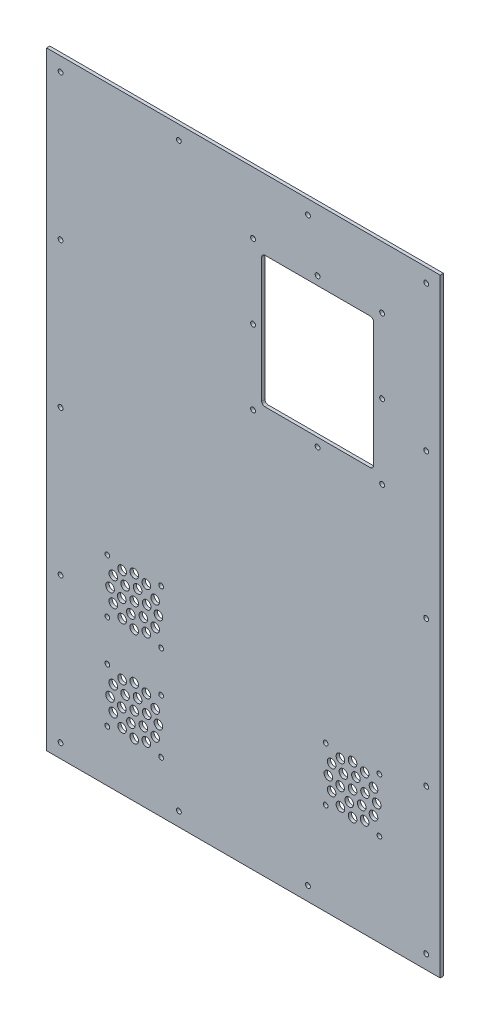
SolidWorks part; units mm, degrees
ref_plane "Спереди" through (0, 0, 0) normal (0, 0, 1) x (1, 0, 0)
ref_plane "Сверху" through (0, 0, 0) normal (0, 1, 0) x (1, 0, 0)
ref_plane "Справа" through (0, 0, 0) normal (1, 0, 0) x (0, 0, -1)
sketch "Эскиз1" plane through (0, 0, 0) normal (0, 0, 1) x (1, 0, 0)
  line L0 (0, 0) -> (366, 0)
  line L1 (0, 0) -> (0, 566)
  line L2 (366, 0) -> (366, 566)
  line L3 (0, 566) -> (366, 566)
  dimension "D1" = 566
  dimension "D2" = 366
extrude "Бобышка-Вытянуть1" add sketch "Эскиз1" along normal blind 3
sketch "Эскиз2" plane through (0, 0, 3) normal (0, 0, 1) x (1, 0, 0)
  line L0 (3, 563) -> (363, 563) construction
  line L1 (3, 563) -> (3, 3) construction
  line L2 (363, 563) -> (363, 3) construction
  line L3 (3, 3) -> (363, 3) construction
  line L4 (0, 566) -> (0, 0) construction
  line L5 (0, 0) -> (366, 0) construction
  dimension "D1" = 560
  dimension "D2" = 360
  dimension "D3" = 3
  dimension "D4" = 3
sketch "Эскиз5" plane through (0, 0, 0) normal (0, 0, -1) x (-1, 0, 0)
  line L0 (-353, 553) -> (-13, 553) construction
  line L1 (-353, 553) -> (-353, 13) construction
  line L2 (-13, 553) -> (-13, 13) construction
  line L3 (-353, 13) -> (-13, 13) construction
  line L4 (-366, 566) -> (0, 566) construction
  line L5 (-366, 0) -> (-366, 566) construction
  line L6 (0, 566) -> (0, 0) construction
  line L7 (0, 0) -> (-366, 0) construction
  line L8 (-366, 23) -> (-343, 23) construction
  line L9 (-366, 23) -> (-366, 0) construction
  line L10 (-343, 23) -> (-343, 0) construction
  line L11 (-366, 0) -> (-343, 0) construction
  line L12 (0, 0) -> (0, 23) construction
  line L13 (0, 0) -> (-23, 0) construction
  line L14 (0, 23) -> (-23, 23) construction
  line L15 (-23, 0) -> (-23, 23) construction
  line L16 (-366, 566) -> (-343, 566) construction
  line L17 (-366, 566) -> (-366, 543) construction
  line L18 (-343, 566) -> (-343, 543) construction
  line L19 (-366, 543) -> (-343, 543) construction
  line L20 (0, 566) -> (0, 543) construction
  line L21 (0, 566) -> (-23, 566) construction
  line L22 (0, 543) -> (-23, 543) construction
  line L23 (-23, 566) -> (-23, 543) construction
  line L24 (-13, 283) -> (-353, 283) construction
  line L25 (-183, 553) -> (-183, 13) construction
  circle A0 centre (-353, 553) radius 2.25
  circle A1 centre (-13, 553) radius 2.25
  circle A3 centre (-243, 553) radius 2.25
  circle A4 centre (-123, 553) radius 2.25
  circle A5 centre (-353, 418) radius 2.25
  circle A6 centre (-353, 283) radius 2.25
  circle A7 centre (-353, 148) radius 2.25
  circle A8 centre (-353, 13) radius 2.25
  circle A11 centre (-13, 418) radius 2.25
  circle A12 centre (-13, 283) radius 2.25
  circle A13 centre (-13, 148) radius 2.25
  circle A14 centre (-13, 13) radius 2.25
  circle A18 centre (-123, 13) radius 2.25
  circle A19 centre (-243, 13) radius 2.25
  dimension "D13" = 4.5
  dimension "D14" = 4.5
  dimension "D15" = 110
  dimension "D17" = 4.5
  dimension "D18" = 4.5
  dimension "D19" = 110
  dimension "D22" = 135
  dimension "D23" = 135
  dimension "D24" = 110
  dimension "D25" = 5
  dimension "D26" = 135
  dimension "D27" = 110
  dimension "D29" = 4.5
  dimension "D31" = 4.5
  dimension "D1" = 13
  dimension "D2" = 13
  dimension "D3" = 13
  dimension "D4" = 13
  dimension "D5" = 23
  dimension "D6" = 23
  dimension "D7" = 23
  dimension "D8" = 23
  dimension "D9" = 23
  dimension "D10" = 23
  dimension "D11" = 23
  dimension "D12" = 23
  dimension "D21" = 5
extrude "Вырез-Вытянуть2" cut sketch "Эскиз5" against normal through all
sketch "Эскиз6" plane through (0, 0, 3) normal (0, 0, 1) x (1, 0, 0)
  line L0 (200, 378.5) -> (200, 500.5) construction
  line L1 (200, 378.5) -> (200, 500.5)
  line L2 (200, 500.5) -> (304, 500.5) construction
  line L3 (200, 500.5) -> (304, 500.5)
  line L4 (304, 500.5) -> (304, 378.5) construction
  line L5 (304, 500.5) -> (304, 378.5)
  line L6 (304, 378.5) -> (200, 378.5) construction
  line L7 (304, 378.5) -> (200, 378.5)
extrude "Вырез-Вытянуть3" cut sketch "Эскиз6" against normal through all
sketch "Эскиз7" plane through (0, 0, 3) normal (0, 0, 1) x (1, 0, 0)
  circle A0 centre (192, 370.5) radius 2.25 construction
  circle A1 centre (192, 370.5) radius 2.25
  circle A2 centre (192, 439.5) radius 2.25 construction
  circle A3 centre (192, 439.5) radius 2.25
  circle A4 centre (192, 508.5) radius 2.25 construction
  circle A5 centre (192, 508.5) radius 2.25
  circle A6 centre (252, 370.5) radius 2.25 construction
  circle A7 centre (252, 370.5) radius 2.25
  circle A8 centre (312, 370.5) radius 2.25 construction
  circle A9 centre (312, 370.5) radius 2.25
  circle A10 centre (252, 508.5) radius 2.25 construction
  circle A11 centre (252, 508.5) radius 2.25
  circle A12 centre (312, 508.5) radius 2.25 construction
  circle A13 centre (312, 508.5) radius 2.25
  circle A14 centre (312, 439.5) radius 2.25 construction
  circle A15 centre (312, 439.5) radius 2.25
  circle A16 centre (312, 370.5) radius 2.25
extrude "Вырез-Вытянуть4" cut sketch "Эскиз7" against normal through all contours A3 | A11 | A13 | A15 | A9 | A7 | A1 | A5 region at (192, 370.5, 3) region at (192, 439.5, 3) region at (252, 370.5, 3) region at (312, 370.5, 3) region at (252, 508.5, 3) region at (312, 508.5, 3) region at (312, 439.5, 3)
fillet "Fillet2" radius 3 4 edges at (200, 378.5, 1.5) (304, 378.5, 1.5) (304, 500.5, 1.5) (200, 500.5, 1.5)
sketch "Эскиз8" plane through (0, 0, 0) normal (0, 0, -1) x (-1, 0, 0)
  line L0 (-81.5, 0) -> (-81.5, 161) construction
  line L1 (0, 0) -> (-366, 0) construction
  line L2 (-81.5, 161) -> (0, 161) construction
  line L3 (0, 566) -> (0, 0) construction
  line L4 (-81.5, 73) -> (0, 73) construction
  line L5 (-81.5, 161) -> (-97.4099, 145.0901) construction
  line L6 (-81.5, 73) -> (-89.9853, 64.5147) construction
  line L7 (-284.5, 0) -> (-284.5, 111) construction
  line L8 (-106.5, 136) -> (-56.5, 136) construction
  line L9 (-106.5, 136) -> (-106.5, 186) construction
  line L10 (-106.5, 186) -> (-56.5, 186) construction
  line L11 (-56.5, 136) -> (-56.5, 186) construction
  line L12 (-106.5, 136) -> (-56.5, 186) construction
  line L13 (-106.5, 186) -> (-56.5, 136) construction
  line L14 (-106.5, 48) -> (-56.5, 48) construction
  line L15 (-106.5, 48) -> (-106.5, 98) construction
  line L16 (-106.5, 98) -> (-56.5, 98) construction
  line L17 (-56.5, 48) -> (-56.5, 98) construction
  line L18 (-106.5, 48) -> (-56.5, 98) construction
  line L19 (-106.5, 98) -> (-56.5, 48) construction
  line L20 (-284.5, 111) -> (-366, 111) construction
  line L21 (-366, 0) -> (-366, 566) construction
  line L22 (-284.5, 111) -> (-292.9853, 102.5147) construction
  line L24 (-309.5, 136) -> (-259.5, 136) construction
  line L25 (-309.5, 136) -> (-309.5, 86) construction
  line L26 (-309.5, 86) -> (-259.5, 86) construction
  line L27 (-259.5, 136) -> (-259.5, 86) construction
  line L28 (-309.5, 136) -> (-259.5, 86) construction
  line L29 (-309.5, 86) -> (-259.5, 136) construction
  circle A0 centre (-81.5, 161) radius 12 construction
  circle A1 centre (-81.5, 161) radius 22.5 construction
  circle A2 centre (-81.5, 138.5) radius 4
  circle A3 centre (-89.9853, 152.5147) radius 4
  circle A4 centre (-81.5, 161) radius 4
  circle A5 centre (-92.75, 141.5144) radius 4
  circle A6 centre (-100.9856, 149.75) radius 4
  circle A7 centre (-104, 161) radius 4
  circle A8 centre (-100.9856, 172.25) radius 4
  circle A9 centre (-92.75, 180.4856) radius 4
  circle A10 centre (-81.5, 183.5) radius 4
  circle A11 centre (-70.25, 180.4856) radius 4
  circle A12 centre (-62.0144, 172.25) radius 4
  circle A13 centre (-59, 161) radius 4
  circle A14 centre (-62.0144, 149.75) radius 4
  circle A15 centre (-70.25, 141.5144) radius 4
  circle A16 centre (-93.0911, 164.1058) radius 4
  circle A17 centre (-84.6058, 172.5911) radius 4
  circle A18 centre (-73.0147, 169.4853) radius 4
  circle A19 centre (-69.9089, 157.8942) radius 4
  circle A20 centre (-78.3942, 149.4089) radius 4
  circle A21 centre (-81.5, 73) radius 12 construction
  circle A22 centre (-81.5, 73) radius 22.5 construction
  circle A23 centre (-81.5, 73) radius 4
  circle A24 centre (-81.5, 50.5) radius 4
  circle A25 centre (-89.9853, 64.5147) radius 4
  circle A26 centre (-92.75, 53.5144) radius 4
  circle A27 centre (-100.9856, 61.75) radius 4
  circle A28 centre (-104, 73) radius 4
  circle A29 centre (-100.9856, 84.25) radius 4
  circle A30 centre (-92.75, 92.4856) radius 4
  circle A31 centre (-81.5, 95.5) radius 4
  circle A32 centre (-70.25, 92.4856) radius 4
  circle A33 centre (-62.0144, 84.25) radius 4
  circle A34 centre (-59, 73) radius 4
  circle A35 centre (-62.0144, 61.75) radius 4
  circle A36 centre (-70.25, 53.5144) radius 4
  circle A37 centre (-93.0911, 76.1058) radius 4
  circle A38 centre (-84.6058, 84.5911) radius 4
  circle A39 centre (-73.0147, 81.4853) radius 4
  circle A40 centre (-69.9089, 69.8942) radius 4
  circle A41 centre (-78.3942, 61.4089) radius 4
  circle A42 centre (-106.5, 186) radius 2.2
  circle A43 centre (-56.5, 186) radius 2.2
  circle A44 centre (-56.5, 136) radius 2.2
  circle A45 centre (-106.5, 136) radius 2.2
  circle A46 centre (-56.5, 98) radius 2.2
  circle A47 centre (-56.5, 48) radius 2.2
  circle A48 centre (-106.5, 48) radius 2.2
  circle A49 centre (-106.5, 98) radius 2.2
  circle A50 centre (-284.5, 111) radius 12 construction
  circle A51 centre (-284.5, 111) radius 22.5 construction
  circle A52 centre (-284.5, 111) radius 4
  circle A53 centre (-284.5, 88.5) radius 4
  circle A54 centre (-292.9853, 102.5147) radius 4
  circle A55 centre (-295.75, 91.5144) radius 4
  circle A56 centre (-303.9856, 99.75) radius 4
  circle A57 centre (-307, 111) radius 4
  circle A58 centre (-303.9856, 122.25) radius 4
  circle A59 centre (-295.75, 130.4856) radius 4
  circle A60 centre (-284.5, 133.5) radius 4
  circle A61 centre (-273.25, 130.4856) radius 4
  circle A62 centre (-265.0144, 122.25) radius 4
  circle A63 centre (-262, 111) radius 4
  circle A64 centre (-265.0144, 99.75) radius 4
  circle A65 centre (-273.25, 91.5144) radius 4
  circle A66 centre (-296.0911, 114.1058) radius 4
  circle A67 centre (-287.6058, 122.5911) radius 4
  circle A68 centre (-276.0147, 119.4853) radius 4
  circle A69 centre (-272.9089, 107.8942) radius 4
  circle A70 centre (-281.3942, 99.4089) radius 4
  circle A71 centre (-309.5, 136) radius 2.2
  circle A72 centre (-259.5, 136) radius 2.2
  circle A73 centre (-259.5, 86) radius 2.2
  circle A74 centre (-309.5, 86) radius 2.2
  point P26 (-81.5, 161)
  point P52 (-81.5, 161)
  point P82 (-81.5, 73)
  point P93 (-81.5, 73)
  point P144 (-284.5, 111)
  point P155 (-284.5, 111)
  dimension "D4" = 45
  dimension "D5" = 24
  dimension "D7" = 8
  dimension "D8" = 8
  dimension "D9" = 8
  dimension "D12" = 8
  dimension "D13" = 8
  dimension "D14" = 8
  dimension "D16" = 24
  dimension "D17" = 45
  dimension "D22" = 4.4
  dimension "D25" = 4.4
  dimension "D28" = 24
  dimension "D29" = 45
  dimension "D30" = 8
  dimension "D31" = 45
  dimension "D36" = 4.4
  dimension "D1" = 73
  dimension "D2" = 161
  dimension "D3" = 81.5
  dimension "D6" = 45
  dimension "D15" = 45
  dimension "D20" = 50
  dimension "D21" = 50
  dimension "D23" = 50
  dimension "D24" = 50
  dimension "D26" = 81.5
  dimension "D27" = 111
  dimension "D34" = 50
  dimension "D35" = 50
  dimension "D10" = 12
  dimension "D11" = 6
  dimension "D18" = 12
  dimension "D19" = 6
  dimension "D32" = 12
  dimension "D33" = 6
extrude "Вырез-Вытянуть5" cut sketch "Эскиз8" against normal through all
